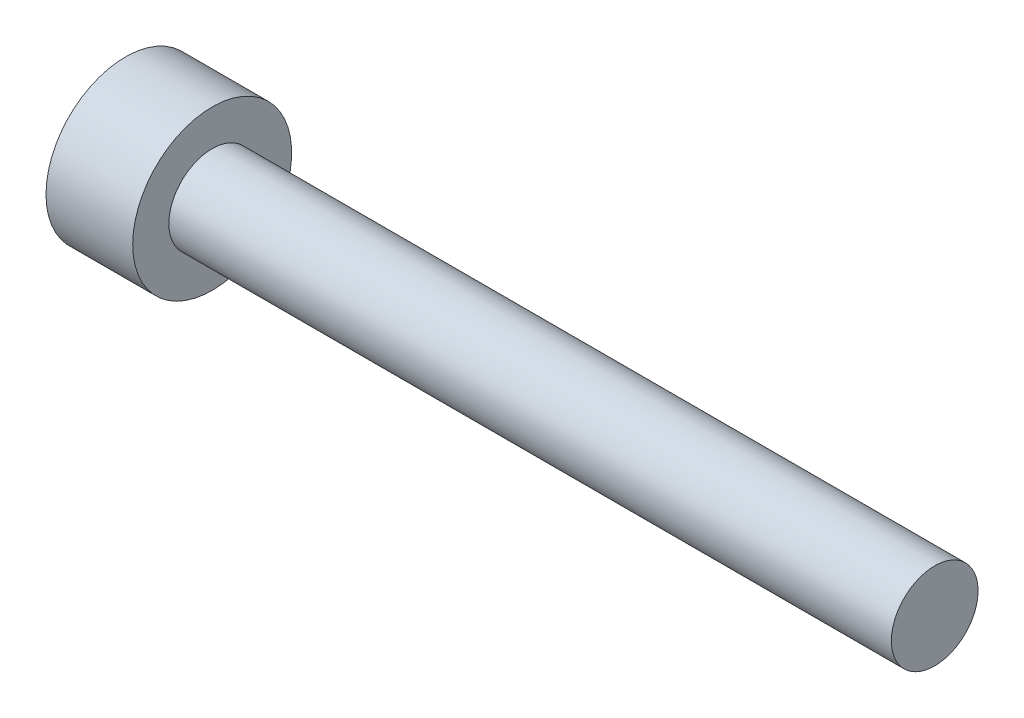
SolidWorks part; units mm, degrees
ref_plane "Front Plane" through (0, 0, 0) normal (0, 0, 1) x (1, 0, 0)
ref_plane "Top Plane" through (0, 0, 0) normal (0, 1, 0) x (1, 0, 0)
ref_plane "Right Plane" through (0, 0, 0) normal (1, 0, 0) x (0, 0, -1)
sketch "Screw Sketch" plane through (0, 0, 0) normal (0, 0, 1) x (1, 0, 0)
  line L0 (-1000, 0) -> (1000, 0) construction
  line L1 (-3, 0) -> (-3, 2.75)
  line L2 (-3, 2.75) -> (0, 2.75)
  line L3 (0, 2.75) -> (0, 1.5)
  line L4 (0, 1.5) -> (25, 1.5)
  line L5 (25, 1.5) -> (25, 0)
  line L6 (25, 0) -> (-3, 0)
revolve "Screw" add sketch "Screw Sketch" angle 360 about L0
ref_axis "Engine Axis" through (26.4, 0, 0) along (-1, 0, 0)
ref_plane "Head Top" through (-3, 0, 0) normal (1, 0, 0) x (0, 0, -1)
sketch "Socket Sketch" plane through (-3, 0, 0) normal (1, 0, 0) x (0, 0, -1)
  line L0 (1.4434, 0) -> (0.7217, 1.25)
  line L1 (0.7217, 1.25) -> (-0.7217, 1.25)
  line L2 (-0.7217, 1.25) -> (-1.4434, 0)
  line L3 (-1.4434, 0) -> (-0.7217, -1.25)
  line L4 (-0.7217, -1.25) -> (0.7217, -1.25)
  line L5 (0.7217, -1.25) -> (1.4434, 0)
extrude "Socket" cut sketch "Socket Sketch" along normal blind 1.5
